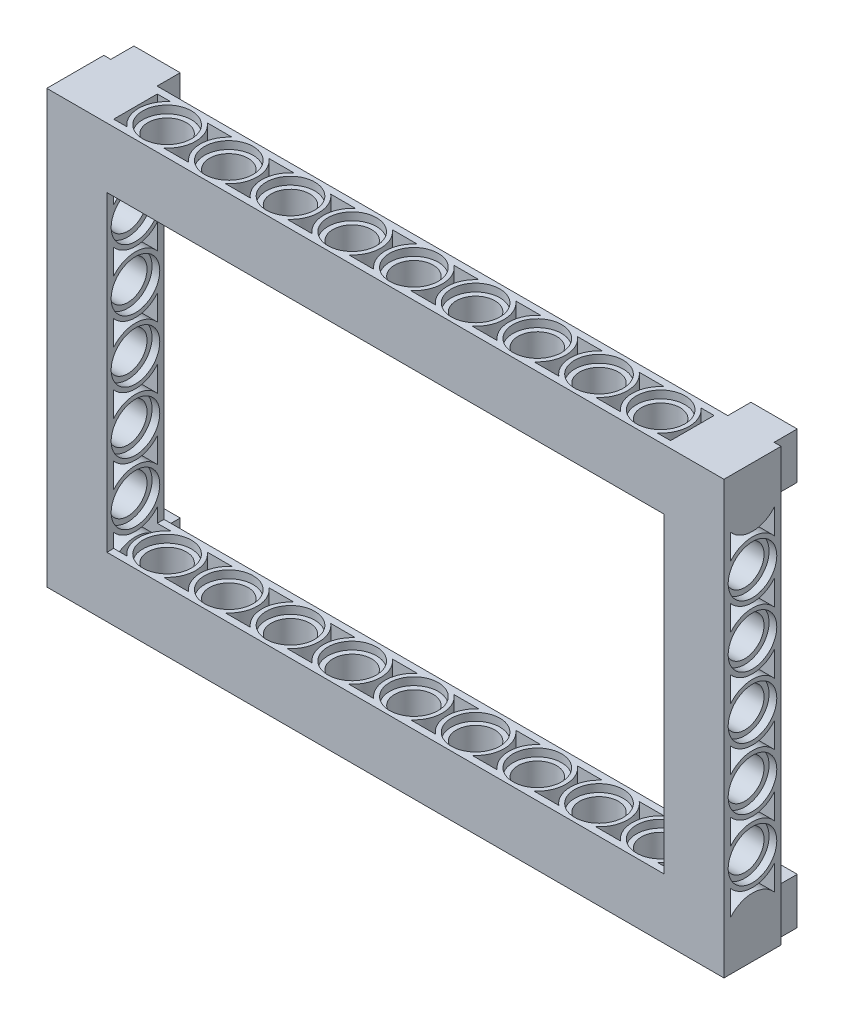
SolidWorks part; units mm, degrees
note: The reader was unsure of these and kept them because the rebuilt part matched: shared geometry of "草图3<3>", "草图3<4>", "草图3<5>", "草图3<6>", "草图7<4>", "草图7<5>", "草图7<6>", "草图7<7>", "草图7<8>".
ref_plane "前视基准面" through (0, 0, 0) normal (0, 0, 1) x (1, 0, 0)
ref_plane "上视基准面" through (0, 0, 0) normal (0, 1, 0) x (1, 0, 0)
ref_plane "右视基准面" through (0, 0, 0) normal (1, 0, 0) x (0, 0, -1)
other "Configuration Table"
sketch "草图1" plane through (0, 0, 0) normal (0, 0, 1) x (1, 0, 0)
  line L0 (-43, 0) -> (43, 0) construction
  line L1 (43, -28) -> (-43, -28) construction
  line L2 (43, -28) -> (43, 28) construction
  line L3 (43, 28) -> (-43, 28) construction
  line L4 (-43, -28) -> (-43, 28) construction
  line L5 (43, -28) -> (-43, 28) construction
  line L6 (43, 28) -> (-43, -28) construction
  line L7 (0, 28) -> (0, -28) construction
  line L9 (-37, 22) -> (-43, 22)
  line L10 (-37, 22) -> (-37, 28)
  line L11 (-37, 28) -> (-43, 28)
  line L12 (-43, 22) -> (-43, 28)
  line L13 (-37, 22) -> (-43, 28) construction
  line L14 (-37, 28) -> (-43, 22) construction
  line L22 (37, 22) -> (43, 22)
  line L23 (37, 22) -> (37, 28)
  line L24 (37, 28) -> (43, 28)
  line L25 (43, 22) -> (43, 28)
  line L26 (37, -22) -> (43, -22)
  line L27 (43, -22) -> (43, -28)
  line L28 (37, -28) -> (43, -28)
  line L29 (37, -22) -> (37, -28)
  line L30 (-37, -28) -> (-43, -28)
  line L31 (-43, -22) -> (-43, -28)
  line L32 (-37, -22) -> (-43, -22)
  line L33 (-37, -22) -> (-37, -28)
  circle A0 centre (-40, 25) radius 0.8
  circle A3 centre (40, 25) radius 0.8
  circle A4 centre (40, -25) radius 0.8
  circle A5 centre (-40, -25) radius 0.8
  point P0 (0, 0)
  dimension "D3" = 1.6
  dimension "D1" = 3
  dimension "D2" = 3
  dimension "D4" = 86
  dimension "D5" = 56
extrude "凸台-拉伸1" add sketch "草图1" along normal blind 3 contours L33 L32 L31 L30 A5 | L12 L9 L10 L11 A0
sketch "草图2" plane through (-43, 0, 0) normal (-1, 0, 0) x (0, 0, 1)
  line L1 (10.4, 28) -> (3, 28)
  line L2 (10.4, 28) -> (10.4, -28)
  line L3 (10.4, -28) -> (3, -28)
  line L4 (3, 28) -> (3, -28)
  line L5 (3, -28) -> (0, -28) construction
  dimension "D2" = 7.4
  dimension "D3" = 3
extrude "凸台-拉伸3" add sketch "草图2" against normal blind 7.8 from offset 0.9
sketch "草图3" plane through (-43, 0, 0) normal (-1, 0, 0) x (0, 0, 1)
  line L0 (3, 0) -> (10.4, 0) construction
  line L1 (3, 28) -> (3, -28) construction
  line L2 (10.4, -28) -> (10.4, 28) construction
  line L8 (3.55, 0) -> (4.2, 0)
  line L9 (3.875, 0) -> (3.875, 5.6106)
  line L10 (9.2, 0) -> (9.85, 0)
  line L11 (9.525, 0) -> (9.525, 5.6106)
  circle A0 centre (6.7, 0) radius 2.5
  circle A1 centre (6.7, 0) radius 3.15
  circle A2 centre (6.7, 8) radius 2.5
  circle A3 centre (6.7, 8) radius 3.15
  circle A4 centre (6.7, 0) radius 3.7
  circle A5 centre (6.7, 8) radius 3.7
  point P21 (3.875, 0)
  point P25 (9.525, 0)
  dimension "D1" = 5
  dimension "D2" = 6.3
  dimension "D4" = 7.4
  dimension "D3" = 8
extrude "切除-拉伸1" cut sketch "草图3" against normal up to next (6.9 mm away) from surface at 0.9 contours A0 starting at face at (-43.9, 0, 6.7)
extrude "切除-拉伸2" cut sketch "草图3<3>" against normal blind 1 from surface at 0.9 contours A1 starting at face at (-43.9, 0, 4.2)
sketch "草图3<3>" plane through (-43, 0, 0) normal (-1, 0, 0) x (0, 0, 1) same geometry as "草图3"
extrude "切除-拉伸3" cut sketch "草图3<4>" along normal blind 1 from surface at -6.9 contours A1 | A0 starting at face at (-36.1, 0, 4.2)
sketch "草图3<4>" plane through (-43, 0, 0) normal (-1, 0, 0) x (0, 0, 1) same geometry as "草图3"
pattern_linear "阵列(线性)1" count 3 spacing 8 along (0, 1, 0) of "切除-拉伸1", "切除-拉伸2", "切除-拉伸3"
pattern_linear "阵列(线性)2" count 3 spacing 8 along (0, -1, 0) of "切除-拉伸1", "切除-拉伸2", "切除-拉伸3"
extrude "切除-拉伸4" cut sketch "草图3<5>" against normal blind 2 from surface at 0.9
sketch "草图3<5>" plane through (-43, 0, 0) normal (-1, 0, 0) x (0, 0, 1) same geometry as "草图3"
extrude "切除-拉伸5" cut sketch "草图3<6>" along normal blind 2 from surface at -6.9
sketch "草图3<6>" plane through (-43, 0, 0) normal (-1, 0, 0) x (0, 0, 1) same geometry as "草图3"
pattern_linear "阵列(线性)3" count 3 spacing 8 along (0, 1, 0) of "切除-拉伸4", "切除-拉伸5"
pattern_linear "阵列(线性)4" count 4 spacing 8 along (0, -1, 0) of "切除-拉伸4", "切除-拉伸5"
mirror "镜向6" about plane through (0, 0, 0) normal (1, 0, 0) of bodies 123 133
sketch "草图7" plane through (0, -28, 0) normal (0, -1, 0) x (1, 0, 0)
  line L0 (-36.1, 10.4) -> (-43.9, 10.4) construction
  line L1 (-40, 9.85) -> (-40, 9.2)
  line L2 (-43.9, 6.7) -> (43.9, 6.7) construction
  line L3 (-43.9, 3) -> (-43.9, 10.4) construction
  line L4 (-43.9, 3) -> (-36.1, 3) construction
  line L5 (-40, 10.4) -> (40, 10.4)
  line L6 (-40, 10.4) -> (-40, 3) construction
  line L7 (-40, 3) -> (40, 3)
  line L8 (40, 10.4) -> (40, 3)
  line L9 (-40, 9.525) -> (-34.3894, 9.525)
  line L10 (40, 10.4) -> (43.9, 10.4)
  line L11 (40, 10.4) -> (40, 3)
  line L12 (40, 3) -> (43.9, 3)
  line L13 (43.9, 10.4) -> (43.9, 3)
  line L14 (-40, 3.875) -> (-34.3894, 3.875)
  circle A0 centre (-32, 6.7) radius 3.7
  circle A1 centre (-32, 6.7) radius 3.15
  circle A2 centre (-40, 6.7) radius 2.5
  circle A3 centre (-40, 6.7) radius 3.15
  circle A4 centre (-40, 6.7) radius 3.7
  circle A5 centre (-32, 6.7) radius 2.5
  line M24 (-37, 3) -> (-43, 3)
  dimension "D3" = 5
  dimension "D4" = 6.3
  dimension "D5" = 7.4
  dimension "D1" = 80
  dimension "D2" = 3.9
  dimension "D6" = 8
extrude "凸台-拉伸5" add sketch "草图7" against normal blind 7.8 contours A0 L7 L8 L2 | A0 L2 L8 L5 | A4 L2 A0 L5 | A4 L7 A0 L2 M24
extrude "切除-拉伸6" cut sketch "草图7<4>" against normal blind 2 contours A4 L14 A0 L9
sketch "草图7<4>" plane through (0, -28, 0) normal (0, -1, 0) x (1, 0, 0) same geometry as "草图7"
extrude "切除-拉伸7" cut sketch "草图7<5>" along normal blind 2 from surface contours A4 L14 A0 L9
sketch "草图7<5>" plane through (0, -28, 0) normal (0, -1, 0) x (1, 0, 0) same geometry as "草图7"
extrude "切除-拉伸8" cut sketch "草图7<6>" against normal blind 1 contours A1 A5
sketch "草图7<6>" plane through (0, -28, 0) normal (0, -1, 0) x (1, 0, 0) same geometry as "草图7"
extrude "切除-拉伸9" cut sketch "草图7<7>" along normal blind 1 from surface contours A1 A5
sketch "草图7<7>" plane through (0, -28, 0) normal (0, -1, 0) x (1, 0, 0) same geometry as "草图7"
extrude "切除-拉伸10" cut sketch "草图7<8>" against normal up to next contours A5
sketch "草图7<8>" plane through (0, -28, 0) normal (0, -1, 0) x (1, 0, 0) same geometry as "草图7"
pattern_linear "阵列(线性)5" count 9 spacing 8 along (1, 0, 0) of "切除-拉伸8", "切除-拉伸9", "切除-拉伸10"
pattern_linear "阵列(线性)6" count 10 spacing 8 along (1, 0, 0) of "切除-拉伸6", "切除-拉伸7"
mirror "镜向8" about plane through (0, 0, 0) normal (0, 1, 0) of bodies 145
